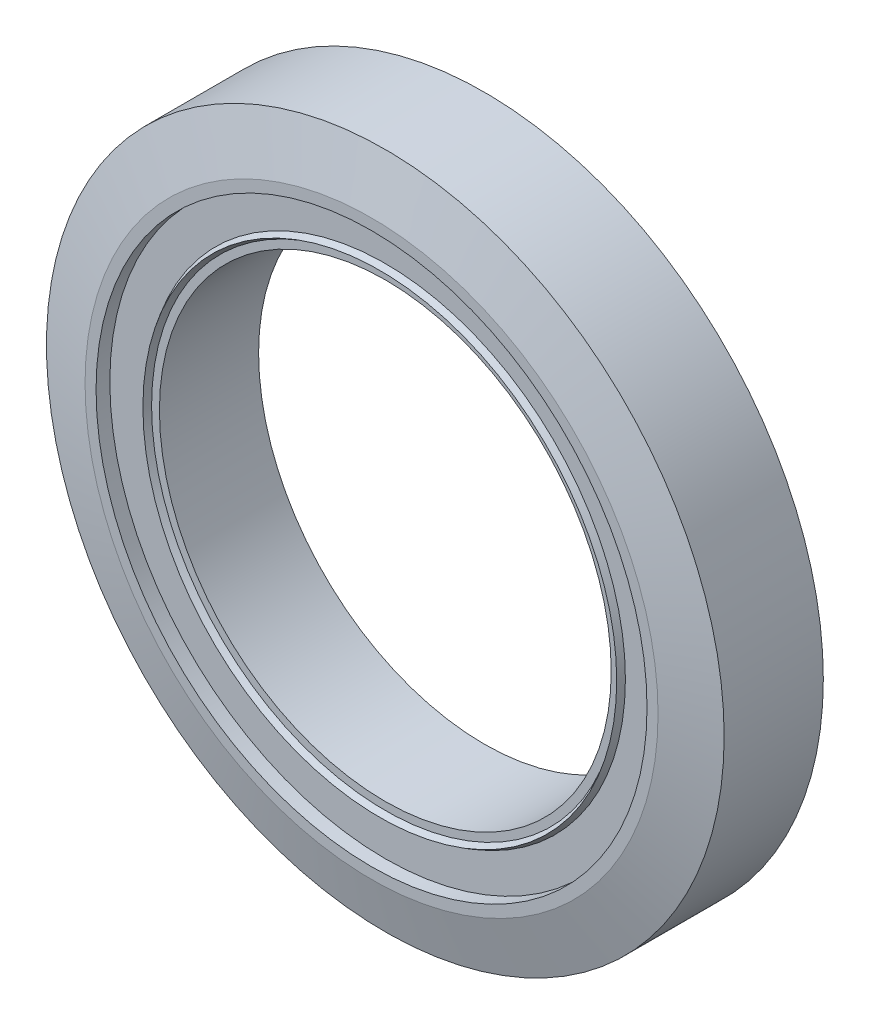
SolidWorks part; units mm, degrees
material "HPU"
ref_plane "Front Plane" through (0, 0, 0) normal (0, 0, 1) x (1, 0, 0)
ref_plane "Top Plane" through (0, 0, 0) normal (0, 1, 0) x (1, 0, 0)
ref_plane "Right Plane" through (0, 0, 0) normal (1, 0, 0) x (0, 0, -1)
sketch "Sketch2" plane through (0, 0, 0) normal (1, 0, 0) x (0, 0, -1)
  line L0 (0, 0) -> (0, 7.502) construction
  line L1 (-0.9, 6.15) -> (0.9, 6.15)
  line L2 (-1.15, 5.2) -> (-0.9, 6.15)
  line L3 (-0.9, 4.1) -> (0.9, 4.1)
  line L4 (-1, 4.3) -> (1, 4.3) construction
  line L5 (0, 0) -> (5.5331, 0) construction
  line L6 (1, 4.3) -> (0.9, 4.2423)
  line L7 (1.15, 5.2) -> (0.9, 6.15)
  line L8 (1.15, 5) -> (0.9, 5)
  line L9 (0.9, 5) -> (0.9, 4.3577)
  line L10 (1, 4.3) -> (0.9, 4.3577)
  line L11 (1.15, 5) -> (1.15, 5.2)
  line L12 (-1, 4.3) -> (-0.9, 4.3577)
  line L13 (-0.9, 5) -> (-0.9, 4.3577)
  line L14 (-1.15, 5) -> (-0.9, 5)
  line L15 (-1.15, 5) -> (-1.15, 5.2)
  line L16 (-1, 4.3) -> (-0.9, 4.2423)
  line L17 (-0.9, 4.2423) -> (-0.9, 4.1)
  line L18 (0.9, 4.2423) -> (0.9, 4.1)
  dimension "D1" = 2.3
  dimension "D2" = 12.3
  dimension "D3" = 8.2
  dimension "D4" = 10.4
  dimension "D5" = 1.8
  dimension "D6" = 1.8
  dimension "D7" = 0.2
  dimension "D8" = 8.6
  dimension "D9" = 2
  dimension "D10" = 60
revolve "Revolve2" add sketch "Sketch2" angle 360 about L5
ref_axis "Axis1" through (0, 0, -1.265) along (0, 0, 1)
